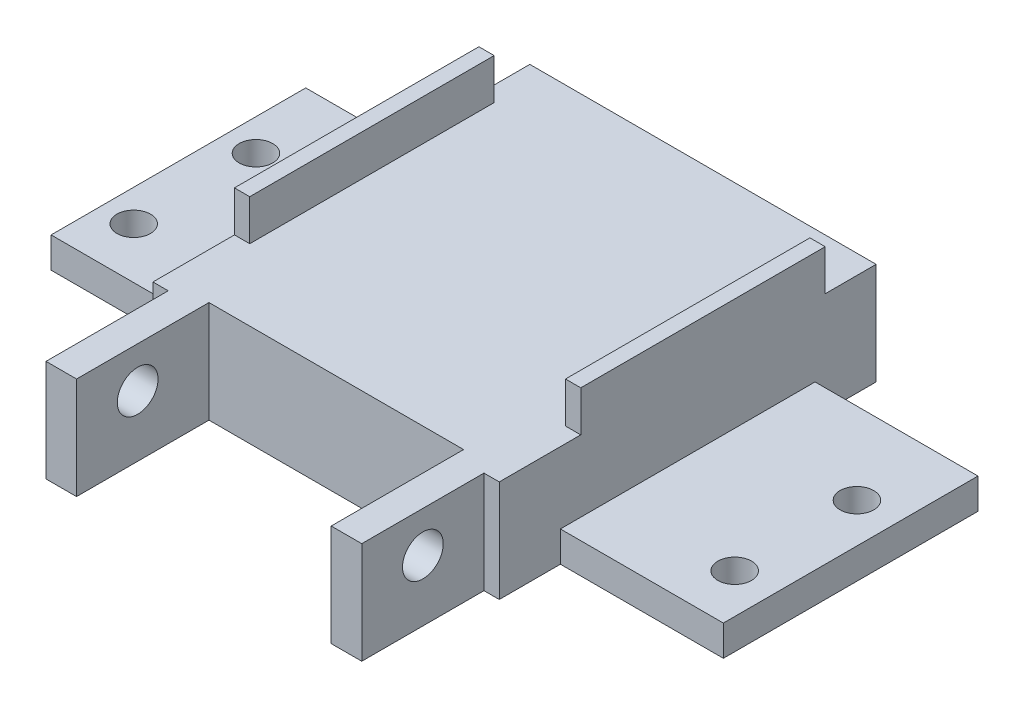
SolidWorks part; units mm, degrees
ref_plane "前视基准面" through (0, 0, 0) normal (0, 0, 1) x (1, 0, 0)
ref_plane "上视基准面" through (0, 0, 0) normal (0, 1, 0) x (1, 0, 0)
ref_plane "右视基准面" through (0, 0, 0) normal (1, 0, 0) x (0, 0, -1)
sketch "草图1" plane through (0, 0, 0) normal (0, 1, 0) x (1, 0, 0)
  line L1 (17, -24.5) -> (-17, -24.5)
  line L2 (17, -24.5) -> (17, 24.5)
  line L3 (17, 24.5) -> (-17, 24.5)
  line L4 (-17, -24.5) -> (-17, 24.5)
  line L5 (0, 24.5) -> (0, -24.5) construction
  line L6 (17, 0) -> (-17, 0) construction
  point P0 (0, 0)
  dimension "D1" = 49
  dimension "D2" = 34
extrude "凸台-拉伸1" add sketch "草图1" along normal blind 10
sketch "草图2" plane through (0, 10, 0) normal (0, 1, 0) x (1, 0, 0)
  line L0 (-17, 24.5) -> (-17, -24.5) construction
  line L1 (-17, 19.5) -> (-15.5, 19.5)
  line L2 (-17, 19.5) -> (-17, -4.5)
  line L3 (-17, -4.5) -> (-15.5, -4.5)
  line L4 (-15.5, 19.5) -> (-15.5, -4.5)
  line L5 (17, 24.5) -> (-17, 24.5) construction
  line L6 (0, -55) -> (0, 55) construction
  line L7 (17, -4.5) -> (15.5, -4.5)
  line L8 (15.5, 19.5) -> (15.5, -4.5)
  line L9 (17, 19.5) -> (17, -4.5)
  line L10 (17, 19.5) -> (15.5, 19.5)
  dimension "D1" = 1.5
  dimension "D2" = 24
  dimension "D3" = 5
extrude "凸台-拉伸2" add sketch "草图2" along normal blind 4
sketch "草图3" plane through (0, 10, 0) normal (0, 1, 0) x (1, 0, 0)
  line L0 (-17, -24.5) -> (17, -24.5) construction
  line L1 (-17, -24.5) -> (-15.5, -24.5)
  line L2 (-17, -24.5) -> (-17, -12.5)
  line L3 (-17, -12.5) -> (-15.5, -12.5)
  line L4 (-15.5, -24.5) -> (-15.5, -12.5)
  line L5 (17, -24.5) -> (15.5, -24.5)
  line L6 (17, -24.5) -> (17, -12.5)
  line L7 (17, -12.5) -> (15.5, -12.5)
  line L8 (15.5, -24.5) -> (15.5, -12.5)
  line L10 (-12.5, -24.5) -> (12.5, -24.5)
  line L11 (-12.5, -24.5) -> (-12.5, -11.5)
  line L12 (-12.5, -11.5) -> (12.5, -11.5)
  line L13 (12.5, -24.5) -> (12.5, -11.5)
  dimension "D1" = 1.5
  dimension "D2" = 1.5
  dimension "D3" = 12
  dimension "D4" = 12
  dimension "D5" = 13
  dimension "D6" = 3
  dimension "D7" = 3
extrude "切除-拉伸1" cut sketch "草图3" against normal up to surface (10 mm away) up to face at (0, 0, 0)
sketch "草图4" plane through (-15.5, 0, 0) normal (-1, 0, 0) x (0, 0, 1)
  line L0 (24.5, 0) -> (24.5, 10) construction
  line L1 (24.5, 10) -> (12.5, 10) construction
  circle A0 centre (18.5, 6) radius 2
  dimension "D1" = 6
  dimension "D2" = 4
  dimension "D3" = 4
extrude "切除-拉伸2" cut sketch "草图4" against normal up to surface (31 mm away) up to face at (15.5, 5, 18.5)
sketch "草图5" plane through (0, 0, 0) normal (0, -1, 0) x (1, 0, 0)
  line L0 (-12.5, 11.5) -> (12.5, 11.5) construction
  line L1 (4, 11.5) -> (-4, 11.5)
  line L2 (4, 11.5) -> (4, 41.5)
  line L4 (-4, 11.5) -> (-4, 41.5)
  line L5 (13, 41.5) -> (4, 41.5)
  line L7 (13, 41.5) -> (13, 56.5)
  line L8 (13, 56.5) -> (-13, 56.5)
  line L9 (-13, 41.5) -> (-13, 56.5)
  line L10 (-4, 41.5) -> (-13, 41.5)
  point P6 (0, 11.5)
  dimension "D1" = 8
  dimension "D2" = 30
  dimension "D3" = 26
  dimension "D4" = 15
  dimension "D5" = 9
extrude "凸台-拉伸3" add sketch "草图5" against normal blind 8
extrude "切除-拉伸4" cut sketch "草图5<2>" against normal up to surface (10 mm away) up to face at (0, 10, 3.1)
sketch "草图5<2>" plane through (0, 0, 0) normal (0, -1, 0) x (1, 0, 0) same geometry as "草图5"
sketch "草图6" plane through (0, 0, 0) normal (0, -1, 0) x (1, 0, 0)
  line L0 (17, 12.5) -> (17, -24.5) construction
  line L1 (17, 6.5) -> (33, 6.5)
  line L2 (17, 6.5) -> (17, -18.5)
  line L3 (17, -18.5) -> (33, -18.5)
  line L4 (33, 6.5) -> (33, -18.5)
  line L5 (0, 11.5) -> (0, -24.5) construction
  line L6 (-12.5, 11.5) -> (12.5, 11.5) construction
  line L7 (17, -24.5) -> (-17, -24.5) construction
  line L8 (-17, -18.5) -> (-33, -18.5)
  line L9 (-33, 6.5) -> (-33, -18.5)
  line L10 (-17, 6.5) -> (-33, 6.5)
  line L11 (-17, 6.5) -> (-17, -18.5)
  dimension "D1" = 16
  dimension "D2" = 25
  dimension "D3" = 6
extrude "凸台-拉伸4" add sketch "草图6" against normal blind 3
sketch "草图7" plane through (0, 0, 0) normal (0, -1, 0) x (1, 0, 0)
  line L0 (-12.5, 11.5) -> (12.5, 11.5) construction
  line L1 (29.1124, 1.5) -> (-29.8876, 1.5) construction
  line L2 (29.1124, 1.5) -> (29.1124, -10.5) construction
  line L3 (29.1124, -10.5) -> (-29.8876, -10.5) construction
  line L4 (-29.8876, 1.5) -> (-29.8876, -10.5) construction
  line L5 (29.1124, 1.5) -> (-29.8876, -10.5) construction
  line L6 (29.1124, -10.5) -> (-29.8876, 1.5) construction
  circle A0 centre (29.1124, 1.5) radius 1.65
  circle A1 centre (29.1124, -10.5) radius 1.65
  circle A2 centre (-29.8876, 1.5) radius 1.65
  circle A3 centre (-29.8876, -10.5) radius 1.65
  point P0 (-0.3876, -4.5)
  dimension "D4" = 3.3
  dimension "D1" = 59
  dimension "D2" = 12
  dimension "D3" = 16
extrude "切除-拉伸5" cut sketch "草图7" against normal blind 8
